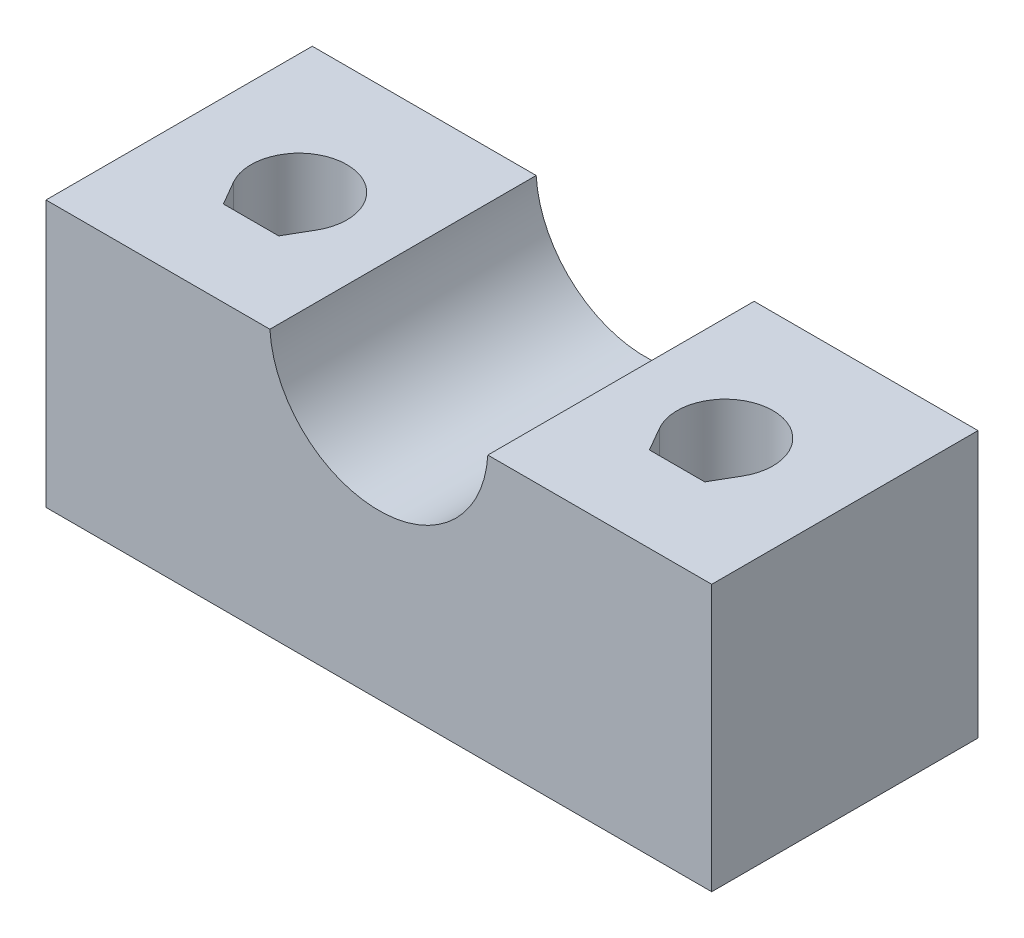
SolidWorks part; units mm, degrees
ref_plane "Piano frontale" through (0, 0, 0) normal (0, 0, 1) x (1, 0, 0)
ref_plane "Piano superiore" through (0, 0, 0) normal (0, 1, 0) x (1, 0, 0)
ref_plane "Piano destro" through (0, 0, 0) normal (1, 0, 0) x (0, 0, -1)
sketch "Schizzo1" plane through (0, 0, 0) normal (0, 0, 1) x (1, 0, 0)
  line L0 (0, 5.25) -> (0, -5) construction
  line L1 (-12.5, -5) -> (12.5, -5)
  line L2 (-12.5, -5) -> (-12.5, 5)
  line L3 (-12.5, 5) -> (-4.0924, 5)
  line L4 (12.5, -5) -> (12.5, 5)
  line L5 (-12.5, -5) -> (12.5, 5) construction
  line L6 (-12.5, 5) -> (12.5, -5) construction
  line L7 (4.0924, 5) -> (12.5, 5)
  line L8 (-4.0924, 5) -> (4.0924, 5) construction
  arc A0 (-4.0924, 5) -> (4.0924, 5) centre (0, 5.25) ccw
  point P0 (0, 0)
  dimension "D3" = 4.1
  dimension "D1" = 10
  dimension "D2" = 25
  dimension "D4" = 0.25
extrude "Main body" add sketch "Schizzo1" along normal mid plane 10 contours L7 L4 L1 L2 L3 A0
sketch "Schizzo2" plane through (0, -5, 0) normal (0, -1, 0) x (1, 0, 0)
  line L0 (0, 5) -> (0, -5) construction
  line L1 (-12.5, 5) -> (12.5, 5) construction
  line L2 (-12.5, -5) -> (12.5, -5) construction
  line L3 (-12.5, 0) -> (12.5, 0) construction
  line L4 (-12.5, 5) -> (-12.5, -5) construction
  line L5 (12.5, 5) -> (12.5, -5) construction
  line L6 (-8, -1.8) -> (-8, 1.8) construction
  line L7 (-6.9608, 1.8) -> (-6.4412, 0.9)
  line L8 (-9.0392, 1.8) -> (-9.5588, 0.9)
  line L9 (-6.9608, 1.8) -> (-9.0392, 1.8)
  line L10 (6.9608, 1.8) -> (9.0392, 1.8)
  line L11 (9.0392, 1.8) -> (9.5588, 0.9)
  line L12 (6.9608, 1.8) -> (6.4412, 0.9)
  arc A0 (-9.5588, 0.9) -> (-6.4412, 0.9) centre (-8, 0) ccw
  arc A1 (9.5588, 0.9) -> (6.4412, 0.9) centre (8, 0) cw
  point P22 (8, 1.8)
  point P24 (-8, 1.8)
  dimension "D2" = 3.6
  dimension "D1" = 8
  dimension "D3" = 120
extrude "screw holes" cut sketch "Schizzo2" against normal up to next contours A0 L7 L9 L8 | A1 L12 L10 L11
ref_axis "y rod axis" through (0, 5.25, 5) along (0, 0, -1)
ref_axis "Screw1 hole" through (8, 5, 0) along (0, -1, 0)
ref_axis "Screw 2 hole" through (-8, 5, 0) along (0, -1, 0)
